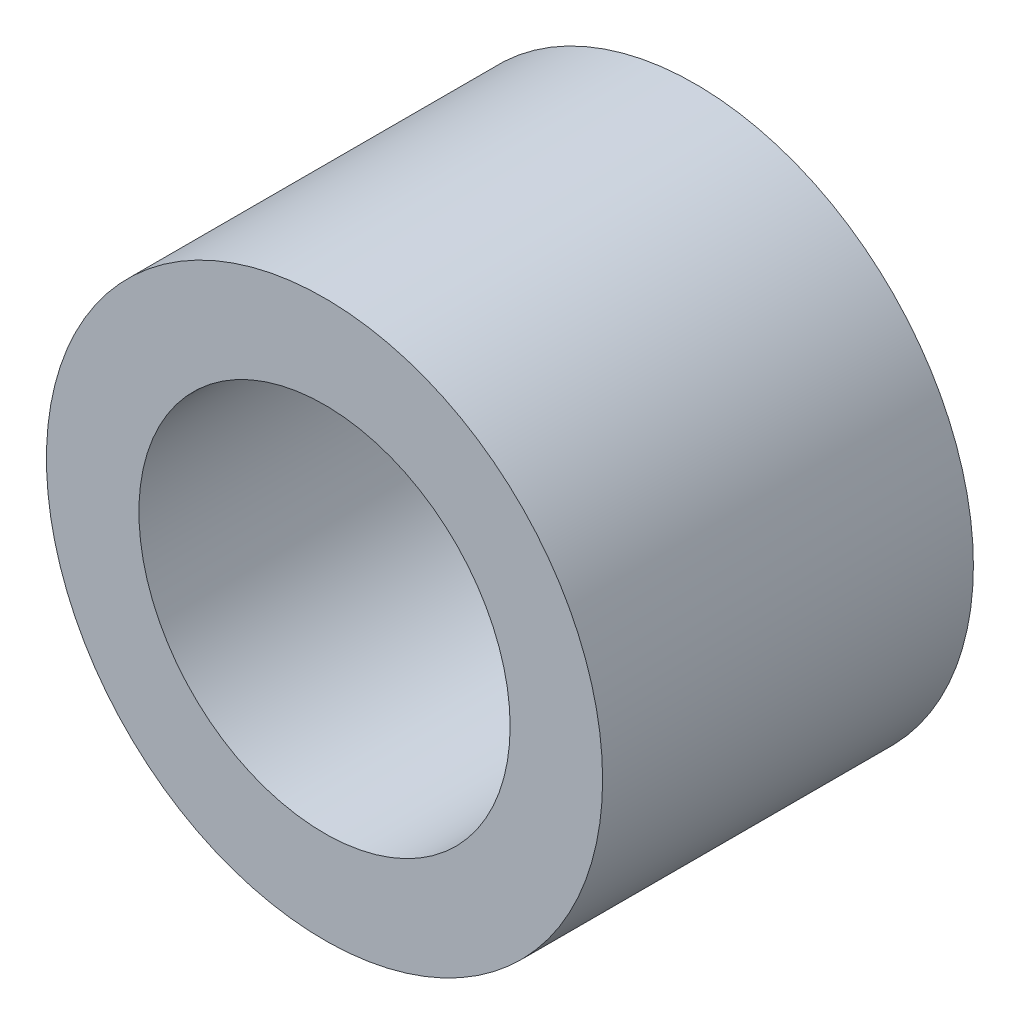
SolidWorks part; units mm, degrees
ref_plane "Front Plane" through (0, 0, 0) normal (0, 0, 1) x (1, 0, 0)
ref_plane "Top Plane" through (0, 0, 0) normal (0, 1, 0) x (1, 0, 0)
ref_plane "Right Plane" through (0, 0, 0) normal (1, 0, 0) x (0, 0, -1)
sketch "Sketch1" plane through (0, 0, 0) normal (0, 0, 1) x (1, 0, 0)
  circle A0 centre (0, 0) radius 4.7625
  circle A1 centre (0, 0) radius 3.1788
  point P4 (0, 4.7625)
  dimension "OD" = 9.525
  dimension "ID" = 6.3576
sketch "Sketch2" plane through (0, 0, 0) normal (1, 0, 0) x (0, 0, -1)
  line L0 (3.175, 0) -> (-3.175, 0) construction
  line L1 (3.175, 4.7625) -> (-3.175, 4.7625) construction
  point P4 (0, 0)
  point P9 (0, 4.7625)
  dimension "Length" = 6.35
sketch "Sketch3" plane through (0, 0, 0) normal (0, 0, 1) x (1, 0, 0)
  circle A0 centre (0, 0) radius 4.7625 construction
  circle A1 centre (0, 0) radius 3.1788 construction
  circle A2 centre (0, 0) radius 4.7625
  circle A3 centre (0, 0) radius 3.1788
extrude "Boss-Extrude1" add sketch "Sketch3" against normal up to vertex (3.175 mm away) and the other way up to vertex (3.175 mm away) up to point (0, 0, -3.175) other way up to point (0, 0, 3.175)
